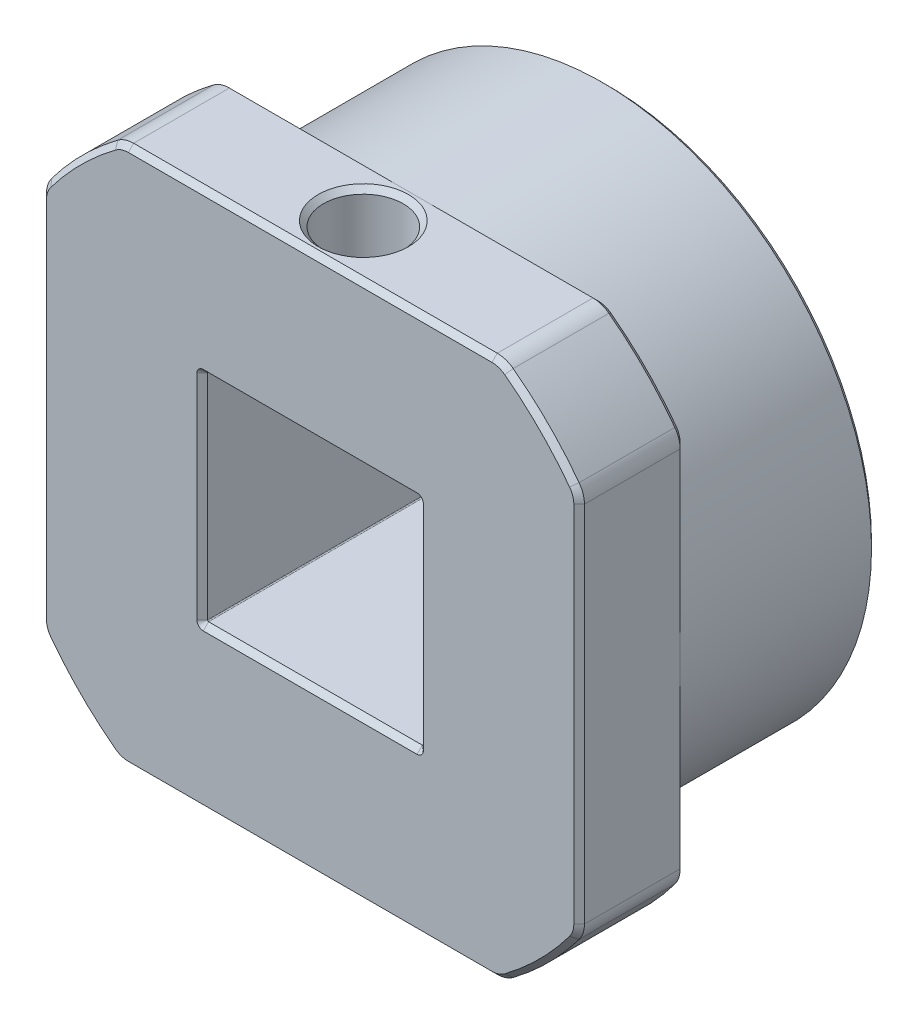
SolidWorks part; units mm, degrees
ref_plane "Front" through (0, 0, 0) normal (0, 0, 1) x (1, 0, 0)
ref_plane "Top" through (0, 0, 0) normal (0, 1, 0) x (1, 0, 0)
ref_plane "Right" through (0, 0, 0) normal (1, 0, 0) x (0, 0, -1)
sketch "Skizze1" plane through (0, 0, 0) normal (0, 0, 1) x (1, 0, 0)
  line L1 (-10.15, -10.15) -> (10.15, -10.15)
  line L2 (-10.15, -10.15) -> (-10.15, 10.15)
  line L3 (-10.15, 10.15) -> (10.15, 10.15)
  line L4 (10.15, -10.15) -> (10.15, 10.15)
  line L5 (-10.15, -10.15) -> (10.15, 10.15) construction
  line L6 (-10.15, 10.15) -> (10.15, -10.15) construction
  circle A0 centre (0, 0) radius 25.3
  point P0 (0, 0)
  dimension "D2" = 50.6
  dimension "D1" = 20.3
extrude "Aufsatz-Linear austragen1" add sketch "Skizze1" along normal blind 18
sketch "Skizze2" plane through (0, 0, 18) normal (0, 0, 1) x (1, 0, 0)
  line L0 (-17.914, 25.3) -> (17.914, 25.3)
  line L1 (-10.15, -10.15) -> (10.15, -10.15)
  line L2 (-10.15, -10.15) -> (-10.15, 10.15)
  line L3 (-10.15, 10.15) -> (10.15, 10.15)
  line L4 (10.15, -10.15) -> (10.15, 10.15)
  line L5 (-10.15, -10.15) -> (10.15, 10.15) construction
  line L6 (-10.15, 10.15) -> (10.15, -10.15) construction
  line L7 (0, 0) -> (13.8508, 0) construction
  line L8 (0, 0) -> (0, 13.2524) construction
  line L9 (25.3, -17.914) -> (25.3, 17.914)
  line L10 (17.914, -25.3) -> (-17.914, -25.3)
  line L11 (-25.3, 17.914) -> (-25.3, -17.914)
  arc A0 (-17.914, 25.3) -> (-25.3, 17.914) centre (0, 0) ccw
  circle A1 centre (0, 0) radius 25.3 construction
  arc A2 (-25.3, -17.914) -> (-17.914, -25.3) centre (0, 0) ccw
  arc A3 (17.914, -25.3) -> (25.3, -17.914) centre (0, 0) ccw
  arc A4 (25.3, 17.914) -> (17.914, 25.3) centre (0, 0) ccw
  dimension "D1" = 62
extrude "Aufsatz-Linear austragen2" add sketch "Skizze2" along normal blind 10
sketch "Skizze3" plane through (0, 25.3, 0) normal (0, 1, 0) x (1, 0, 0)
  line L0 (0, -18) -> (0, -28) construction
  line L2 (17.914, -28) -> (-17.914, -28) construction
  circle A0 centre (0, -23) radius 2.3
  dimension "D1" = 4.6
  dimension "D2" = 10
extrude "Schnitt-Linear austragen1" cut sketch "Skizze3" against normal up to next
pattern_circular "Kreismuster1" [suppressed] count 2 over 90 reverse direction yes of bodies 103
sketch "Sketch1" plane through (0, -25.3, 0) normal (0, -1, 0) x (1, 0, 0)
  circle A0 centre (0, 23) radius 3.75
  dimension "D1" = 7.5
extrude "Cut-Extrude1" [suppressed] cut sketch "Sketch1" against normal offset from surface (7.95 mm away) 7.2 up to face at (0, -10.15, 14)
extrude "Cut-Extrude2" cut sketch "Sketch1<2>" along normal offset from surface (7.95 mm away) 7.2 from surface up to face at (0, 10.15, 20.7) starting at face at (0, 25.3, 25.3)
sketch "Sketch1<2>" plane through (0, -25.3, 0) normal (0, -1, 0) x (1, 0, 0) same geometry as "Sketch1"
fillet "Verrundung1" radius 0.1 4 edges at (10.15, -10.15, 14) (-10.15, -10.15, 14) (-10.15, 10.15, 14) (10.15, 10.15, 14)
fillet "Verrundung2" radius 2.5 8 edges at (-25.3, -17.914, 23) (-17.914, -25.3, 23) (17.914, -25.3, 23) (25.3, -17.914, 23) (25.3, 17.914, 23) (17.914, 25.3, 23) (-25.3, 17.914, 23) (-17.914, 25.3, 23)
chamfer "Fase1" distance 0.5 angle 45 55 edges at (-10.1207, -10.1207, 0) (-10.15, 0, 0) (-10.1207, 10.1207, 0) (0, 10.15, 0) (10.1207, 10.1207, 0) (10.15, 0, 0) (10.1207, -10.1207, 0) (0, -10.15, 0) (25.3, 0, 0) (-10.1207, 10.1207, 28) (-10.15, 0, 28) (-10.1207, -10.1207, 28) (0, -10.15, 28) (10.1207, -10.1207, 28) (10.15, 0, 28) (10.1207, 10.1207, 28) (0, 10.15, 28) (-25.1717, 17.8906, 28) (-21.9203, 21.9203, 28) (-17.8906, 25.1717, 28) (0, 25.3, 28) (17.8906, 25.1717, 28) (21.9203, 21.9203, 28) (25.1717, 17.8906, 28) (25.3, 0, 28) (25.1717, -17.8906, 28) (21.9203, -21.9203, 28) (17.8906, -25.1717, 28) (0, -25.3, 28) (-17.8906, -25.1717, 28) (-21.9203, -21.9203, 28) (-25.1717, -17.8906, 28) (-25.3, 0, 28) (8.55, 25.3, 18) (-8.55, 25.3, 18) (-17.8906, 25.1717, 18) (17.8906, 25.1717, 18) (-21.9203, 21.9203, 18) (21.9203, 21.9203, 18) (-25.1717, 17.8906, 18) (25.1717, 17.8906, 18) (-25.3, -8.55, 18) (-25.3, 8.55, 18) (25.3, -8.55, 18) (25.3, 8.55, 18) (-25.1717, -17.8906, 18) (25.1717, -17.8906, 18) (-21.9203, -21.9203, 18) (21.9203, -21.9203, 18) (-17.8906, -25.1717, 18) (17.8906, -25.1717, 18) (-8.55, -25.3, 18) (8.55, -25.3, 18) (0, 10.15, 20.7) (0, 25.3, 19.25) tangent propagation no
chamfer "Fase2" [suppressed] distance 0.3 angle 45
chamfer "Fase3" [suppressed] distance 0.5 angle 45
